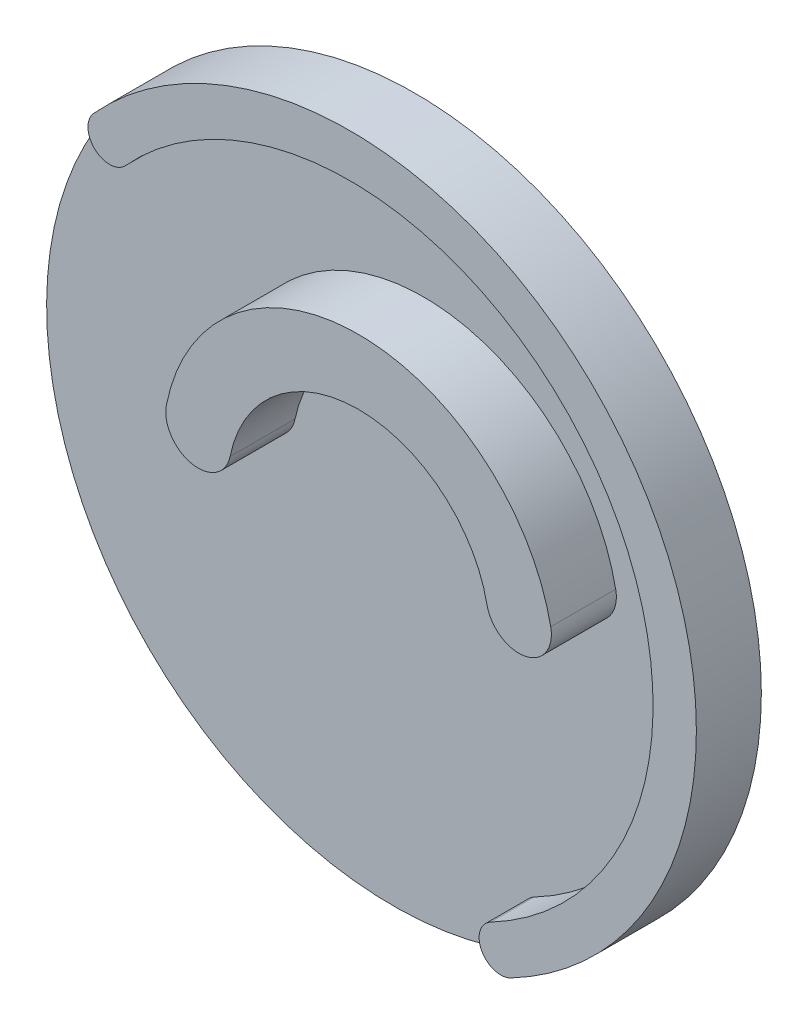
SolidWorks part; units mm, degrees
ref_plane "Front Plane" through (0, 0, 0) normal (0, 0, 1) x (1, 0, 0)
ref_plane "Top Plane" through (0, 0, 0) normal (0, 1, 0) x (1, 0, 0)
ref_plane "Right Plane" through (0, 0, 0) normal (1, 0, 0) x (0, 0, -1)
sketch "Sketch1" plane through (0, 0, 0) normal (0, 0, 1) x (1, 0, 0)
  line L0 (0, 0) -> (0, 4) construction
  line L1 (0, 4) -> (24.6779, 4) construction
  line L2 (0, 0) -> (0.8309, 3.9128)
  line L3 (0.8309, 3.9128) -> (38.4859, -4.0834)
  line L4 (0, 0) -> (0.9717, 3.8802)
  line L5 (0.9717, 3.8802) -> (51.9154, -8.8772) construction
  line L6 (24.6779, 4) -> (26.0802, 11.5527) construction
  line L7 (24.6779, 4) -> (31.01, 8.349) construction
  line L8 (24.6779, 4) -> (20.3289, 10.3321) construction
  line L9 (24.6779, 4) -> (18.6779, 5.5) construction
  line L10 (24.6779, 4) -> (19.3746, 0.818) construction
  line L11 (21.4959, 9.3033) -> (24.6779, 4) construction
  line L12 (0, 0) -> (24.6779, 4) construction
  circle A0 centre (24.6779, 4) radius 16
  arc A1 (18.6779, 5.5) -> (33.4824, 5.5) centre (26.0802, 4) cw construction
  arc A2 (34.9526, 5.7979) -> (17.2078, 5.7979) centre (26.0802, 4) ccw
  arc A3 (32.0123, 5.2021) -> (20.148, 5.2021) centre (26.0802, 4) ccw
  arc A4 (32.0123, 5.2021) -> (34.9526, 5.7979) centre (33.4824, 5.5) ccw
  arc A5 (17.2078, 5.7979) -> (20.148, 5.2021) centre (18.6779, 5.5) ccw
  arc A6 (19.3746, 0.818) -> (29.843, 11.2864) centre (25.6695, 4.9915) cw construction
  arc A7 (30.6719, 12.5366) -> (18.1244, -0.0109) centre (25.6695, 4.9915) ccw construction
  arc A8 (29.0141, 10.0362) -> (20.6248, 1.6469) centre (25.6695, 4.9915) ccw construction
  arc A9 (29.0141, 10.0362) -> (30.6719, 12.5366) centre (29.843, 11.2864) ccw construction
  arc A10 (18.1244, -0.0109) -> (20.6248, 1.6469) centre (19.3746, 0.818) ccw construction
  arc A11 (21.4959, 9.3033) -> (31.9643, -1.1651) centre (25.6695, 3.0085) cw construction
  arc A12 (33.2145, -1.9939) -> (20.6671, 10.5535) centre (25.6695, 3.0085) ccw construction
  arc A13 (30.7141, -0.3362) -> (22.3248, 8.0531) centre (25.6695, 3.0085) ccw construction
  arc A14 (30.7141, -0.3362) -> (33.2145, -1.9939) centre (31.9643, -1.1651) ccw construction
  arc A15 (20.6671, 10.5535) -> (22.3248, 8.0531) centre (21.4959, 9.3033) ccw construction
  point P8 (26.0802, 11.5527)
  point P13 (18.6779, 4)
  point P15 (33.4824, 4)
  point P19 (20.3289, 10.3321)
  point P27 (31.01, 8.349)
  point P39 (0, 0)
  point P40 (51.9154, -8.8772)
  point P43 (38.971, -3.1909)
  point P44 (37.1105, -6.005)
  point P45 (38.3159, -4.367)
  point P46 (38.4859, -4.0834)
  dimension "D3" = 32
  dimension "D4" = 1.5
  dimension "D1" = 4
  dimension "D5" = 45
  dimension "D6" = 45
  dimension "D7" = 6
  dimension "D2" = 25
extrude "Boss-Extrude1" add sketch "Sketch1" against normal blind 1 contours A0
extrude "Boss-Extrude2" add sketch "Sketch1<3>" along normal blind 3 contours A3 A5 A2 A4
sketch "Sketch1<3>" plane through (0, 0, 0) normal (0, 0, 1) x (1, 0, 0) same geometry as "Sketch1"
sketch "Sketch2" plane through (0, 0, 0) normal (0, 0, 1) x (1, 0, 0)
  line L0 (13.5864, 14.0985) -> (24.6779, 4) construction
  line L1 (24.6779, 4) -> (31.6466, -9.283) construction
  line L2 (9.6944, 3.2978) -> (24.6779, 4) construction
  line L3 (36.549, 13.1694) -> (24.6779, 4) construction
  line L4 (39.5558, 2.0896) -> (24.6779, 4) construction
  line L5 (26.5883, 18.8779) -> (24.6779, 4) construction
  arc A0 (9.6944, 3.2978) -> (38.998, -0.4649) centre (24.6779, 4) cw construction
  arc A1 (39.9527, -0.7625) -> (8.6955, 3.251) centre (24.6779, 4) ccw construction
  arc A2 (38.0433, -0.1672) -> (10.6933, 3.3446) centre (24.6779, 4) ccw construction
  arc A3 (38.0433, -0.1672) -> (39.9527, -0.7625) centre (38.998, -0.4649) ccw construction
  arc A4 (8.6955, 3.251) -> (10.6933, 3.3446) centre (9.6944, 3.2978) ccw construction
  arc A5 (23.9758, 18.9836) -> (20.2131, -10.3201) centre (24.6779, 4) cw construction
  arc A6 (19.9154, -11.2748) -> (23.929, 19.9825) centre (24.6779, 4) ccw construction
  arc A7 (20.5107, -9.3654) -> (24.0226, 17.9847) centre (24.6779, 4) ccw construction
  arc A8 (20.5107, -9.3654) -> (19.9154, -11.2748) centre (20.2131, -10.3201) ccw construction
  arc A9 (23.929, 19.9825) -> (24.0226, 17.9847) centre (23.9758, 18.9836) ccw construction
  arc A10 (13.5864, 14.0985) -> (31.6466, -9.283) centre (24.6779, 4) cw construction
  circle A11 centre (24.6779, 4) radius 16 construction
  arc A12 (32.1112, -10.1685) -> (12.847, 14.7717) centre (24.6779, 4) ccw
  arc A13 (31.182, -8.3974) -> (14.3259, 13.4252) centre (24.6779, 4) ccw
  arc A14 (31.182, -8.3974) -> (32.1112, -10.1685) centre (31.6466, -9.283) ccw
  arc A15 (12.847, 14.7717) -> (14.3259, 13.4252) centre (13.5864, 14.0985) ccw
  point P3 (26.5883, 18.8779)
  point P8 (39.5558, 2.0896)
  point P21 (36.549, 13.1694)
  point P33 (29.1514, 18.4141)
  point P34 (39.8759, 2.0747)
  dimension "D2" = 1
  dimension "D1" = 200
  dimension "D3" = 45
  dimension "D4" = 45
extrude "Boss-Extrude3" add sketch "Sketch2" along normal blind 2
equation "\"D6@Sketch1\"=\"D5@Sketch1\""
equation "\"D3@Sketch2\"= \"D5@Sketch1\""
equation "\"D4@Sketch2\"= \"D5@Sketch1\""
